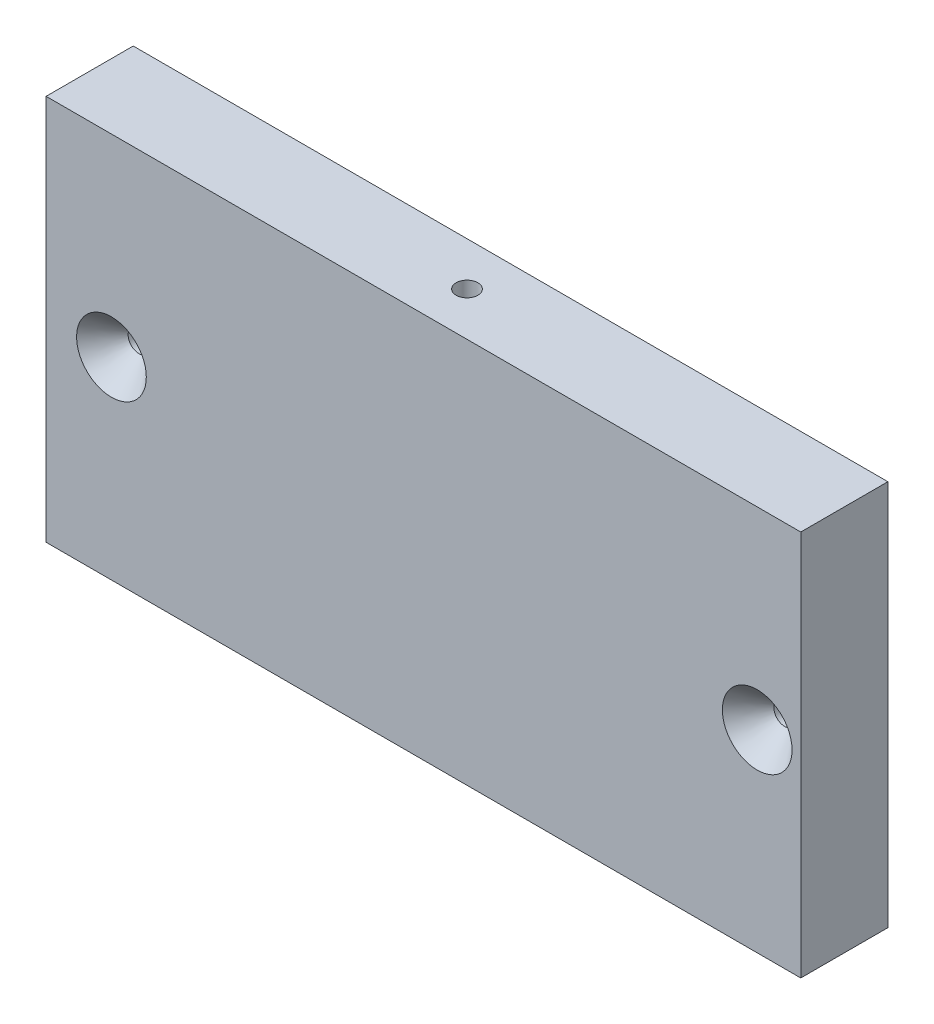
SolidWorks part; units mm, degrees
material "Beech"
ref_plane "Front Plane" through (0, 0, 0) normal (0, 0, 1) x (1, 0, 0)
ref_plane "Top Plane" through (0, 0, 0) normal (0, 1, 0) x (1, 0, 0)
ref_plane "Right Plane" through (0, 0, 0) normal (1, 0, 0) x (0, 0, -1)
sketch "Sketch2" plane through (0, 0, 0) normal (0, 0, 1) x (1, 0, 0)
  line L0 (-231.3045, 12.7) -> (-231.3045, 69)
  line L1 (-341.3045, 12.7) -> (-341.3045, 69)
  line L2 (-341.3045, 69) -> (-231.3045, 69)
  line L7 (-231.3045, 12.7) -> (-341.3045, 12.7)
  dimension "D1" = 56.3
extrude "Boss-Extrude1" add sketch "Sketch2" against normal blind 12.7
hole_wizard "Hole" positions "Sketch4" profile "Sketch5" legacy
sketch "Sketch4" plane through (-124.0045, 277.2867, 0) normal (0, 0, 1) x (-1, 0, 0)
  point P0 (113.65, 236.4367)
  point P2 (207.775, 236.4367)
sketch "Sketch5" plane through (-237.6545, 40.85, 0) normal (1, 0, 0) x (0, -1, 0)
  line L0 (0, 0) -> (0, 32.7039)
  line L1 (0, 32.7039) -> (1.5875, 31.75)
  line L2 (1.5875, 31.75) -> (1.5875, 4.0177)
  line L3 (1.5875, 4.0177) -> (5.08, 0)
  line L4 (5.08, 0) -> (0, 0)
  line L5 (0, -14.3089) -> (0, 102.4216) construction
  line L6 (0, 32.7039) -> (-1.5875, 31.75) construction
  line L7 (-1.5875, 4.0177) -> (-5.08, 0) construction
  dimension "Diameter" = 3.175
  dimension "Depth" = 31.75
  dimension "C-Sink Diameter" = 10.16
  dimension "C-Sink Angle" = 82
  dimension "Drill Angle" = 118
hole_wizard "Hole1" positions "Sketch6" profile "Sketch7" legacy
sketch "Sketch6" plane through (-124.0045, 88.05, -103.8757) normal (0, 1, 0) x (1, 0, 0)
  point P15 (-162.3, -97.5257)
  point P34 (-113.65, -38.7424)
  point P36 (-113.65, 13.691)
  point P54 (162.3, -97.5257)
  point P55 (113.65, -38.7424)
  point P56 (113.65, 13.691)
  point P71 (63.85, 72.4743)
  point P73 (0, 72.4743)
  point P74 (-63.85, 72.4743)
sketch "Sketch7" plane through (-286.3045, 88.05, -6.35) normal (1, 0, 0) x (0, 0, 1)
  line L0 (0, 0) -> (0, 32.7039)
  line L1 (0, 32.7039) -> (1.5875, 31.75)
  line L2 (1.5875, 31.75) -> (1.5875, 4.0177)
  line L3 (1.5875, 4.0177) -> (5.08, 0)
  line L4 (5.08, 0) -> (0, 0)
  line L5 (0, -14.3089) -> (0, 102.4216) construction
  line L6 (0, 32.7039) -> (-1.5875, 31.75) construction
  line L7 (-1.5875, 4.0177) -> (-5.08, 0) construction
  dimension "Diameter" = 3.175
  dimension "Depth" = 31.75
  dimension "C-Sink Diameter" = 10.16
  dimension "C-Sink Angle" = 82
  dimension "Drill Angle" = 118
